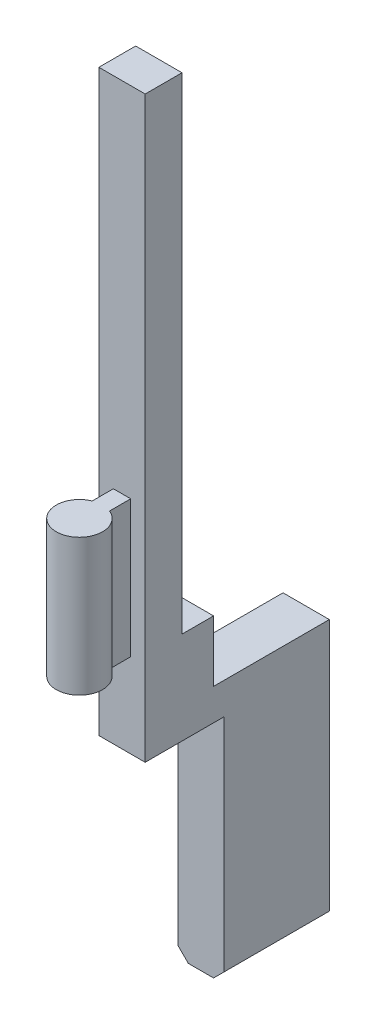
SolidWorks part; units mm, degrees
ref_plane "Płaszczyzna przednia" through (0, 0, 0) normal (0, 0, 1) x (1, 0, 0)
ref_plane "Płaszczyzna górna" through (0, 0, 0) normal (0, 1, 0) x (1, 0, 0)
ref_plane "Płaszczyzna prawa" through (0, 0, 0) normal (1, 0, 0) x (0, 0, -1)
sketch "Szkic1" plane through (0, 0, 0) normal (0, 0, 1) x (1, 0, 0)
  line L1 (-2.2, 10.5) -> (2.2, 10.5)
  line L2 (-2.2, 10.5) -> (-2.2, -10.5)
  line L3 (-2.2, -10.5) -> (2.2, -10.5)
  line L4 (2.2, 10.5) -> (2.2, -10.5)
  line L5 (-2.2, 10.5) -> (2.2, -10.5) construction
  line L6 (-2.2, -10.5) -> (2.2, 10.5) construction
  point P0 (0, 0)
  dimension "D1" = 4.4
  dimension "D2" = 21
extrude "Dodanie-wyciągnięcie1" add sketch "Szkic1" along normal blind 6.5
sketch "Szkic3" plane through (0, 10.5, 0) normal (0, 1, 0) x (1, 0, 0)
  line L0 (0, -6.5) -> (0, -10.55) construction
  line L1 (2.2, -6.5) -> (-2.2, -6.5) construction
  line L3 (0.825, -6.5) -> (0.825, -10.55)
  line L4 (0.825, -6.5) -> (-0.825, -6.5)
  line L5 (-0.825, -6.5) -> (-0.825, -10.55)
  line L6 (0.825, -10.55) -> (-0.825, -10.55)
  line L7 (0.825, -6.5) -> (-0.825, -10.55) construction
  line L8 (-0.825, -6.5) -> (0.825, -10.55) construction
  circle A0 centre (0, -10.55) radius 2.2
  point P5 (0, -8.525)
  line M10 (-2.2, 0) -> (-2.2, -6.5)
  dimension "D2" = 4.4
  dimension "D1" = 4.05
  dimension "D3" = 1.65
extrude "Dodanie-wyciągnięcie2" add sketch "Szkic3" against normal blind 13 contours L5 A0 L3 L6 | L3 A0 L5 L6 | A0 L3 L5 M10 region at (0, 10.5, 7.4519) region at (0, 10.5, 10.8763) region at (0, 10.5, 9.4758)
sketch "Sketch1" plane through (0, 0, 0) normal (0, 0, -1) x (-1, 0, 0)
  line L0 (-2.2, -10.5) -> (-2.2, 10.5) construction
  line L1 (-2.2, -5.5) -> (2.2, -5.5)
  line L2 (-2.2, -5.5) -> (-2.2, -10.5)
  line L3 (-2.2, -10.5) -> (2.2, -10.5)
  line L4 (2.2, -5.5) -> (2.2, -10.5)
  line L5 (0, -10.5) -> (0, -5.5) construction
  line L6 (-2.2, -8) -> (2.2, -8) construction
  line L7 (2.2, 10.5) -> (2.2, -10.5) construction
  line L9 (2.2, -10.5) -> (-2.2, -10.5) construction
  point P460 (0, -8)
  dimension "D1" = 5
extrude "Boss-Extrude1" add sketch "Sketch1" along normal blind 11
sketch "Sketch3" plane through (0, -10.5, 0) normal (0, -1, 0) x (1, 0, 0)
  line L0 (2.2, -11) -> (-2.2, -11) construction
  line L1 (2.2, -11) -> (-2.2, -11)
  line L2 (2.2, -11) -> (2.2, -1)
  line L3 (2.2, -1) -> (-2.2, -1)
  line L4 (-2.2, -11) -> (-2.2, -1)
  line L5 (0, -1) -> (0, -11) construction
  line L6 (2.2, -6) -> (-2.2, -6) construction
  line L7 (2.2, 6.5) -> (2.2, -11) construction
  line L8 (-2.2, 6.5) -> (-2.2, -11) construction
  point P448 (0, -6)
  dimension "D2" = 10
extrude "Boss-Extrude3" add sketch "Sketch3" along normal blind 22
chamfer "Chamfer1" distance 1 angle 45 3 edges at (2.2, -32.5, -6) (-2.2, -32.5, -6) (0, -5.5, -11)
sketch "Sketch5" plane through (0, 10.5, 0) normal (0, 1, 0) x (1, 0, 0)
  line L0 (2.2, -6.5) -> (2.2, 0) construction
  line L1 (-2.2, 0) -> (2.2, 0)
  line L2 (-2.2, 0) -> (-2.2, -3)
  line L3 (-2.2, -3) -> (2.2, -3)
  line L4 (2.2, 0) -> (2.2, -3)
  line L5 (0, -3) -> (0, 0) construction
  line L6 (-2.2, -1.5) -> (2.2, -1.5) construction
  point P212 (0, -1.5)
  dimension "D1" = 3
extrude "Cut-Extrude1" cut sketch "Sketch5" against normal blind 12.2
sketch "Szkic4" plane through (0, 10.5, 0) normal (0, 1, 0) x (1, 0, 0)
  line L0 (-2.2, -6.5) -> (-2.2, -3) construction
  line L1 (-2.2, -3) -> (2.2, -3)
  line L2 (-2.2, -3) -> (-2.2, -6.5)
  line L3 (-2.2, -6.5) -> (2.2, -6.5)
  line L4 (2.2, -3) -> (2.2, -6.5)
  line L5 (-2.2, -3) -> (2.2, -3) construction
  line L6 (2.2, -6.5) -> (2.2, -3) construction
extrude "Dodanie-wyciągnięcie3" add sketch "Szkic4" along normal blind 34
sketch "Szkic5" plane through (-2.2, 0, 0) normal (-1, 0, 0) x (0, 0, 1)
  line L0 (-10, -5.5) -> (0, -5.5) construction
  line L1 (0, -5.5) -> (-11, -5.5)
  line L2 (0, -5.5) -> (0, -7.5)
  line L3 (0, -7.5) -> (-11, -7.5)
  line L4 (-11, -5.5) -> (-11, -7.5)
  line L5 (-11, -31.5) -> (-11, -6.5) construction
  dimension "D1" = 2
extrude "Wytnij-wyciągnięcie1" cut sketch "Szkic5" against normal blind 10
